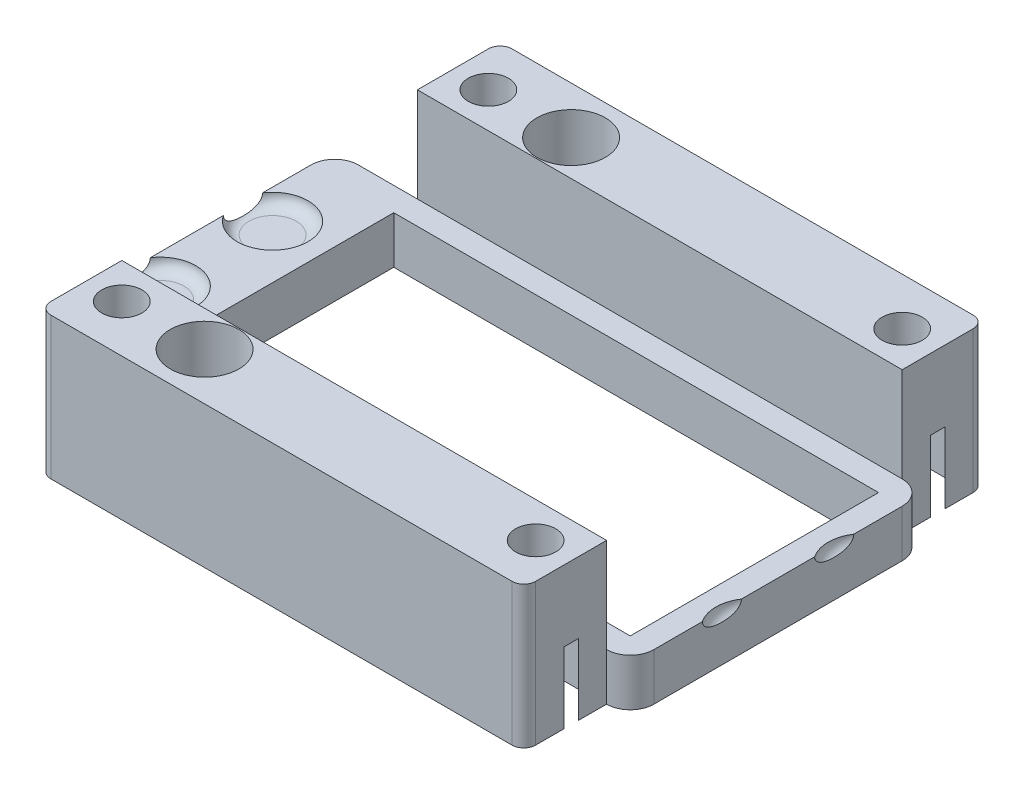
SolidWorks part; units mm, degrees
ref_plane "前视基准面" through (0, 0, 0) normal (0, 0, 1) x (1, 0, 0)
ref_plane "上视基准面" through (0, 0, 0) normal (0, 1, 0) x (1, 0, 0)
ref_plane "右视基准面" through (0, 0, 0) normal (1, 0, 0) x (0, 0, -1)
sketch "草图1" plane through (0, 0, 0) normal (0, 1, 0) x (1, 0, 0)
  line L1 (-20, 10) -> (20, 10)
  line L2 (-20, 10) -> (-20, -10)
  line L3 (-20, -10) -> (20, -10)
  line L4 (20, 10) -> (20, -10)
  line L5 (-20, 10) -> (20, -10) construction
  line L6 (-20, -10) -> (20, 10) construction
  line L7 (-20.5, 10.5) -> (20.5, 10.5)
  line L8 (-20.5, 10.5) -> (-20.5, -10.5)
  line L9 (-20.5, -10.5) -> (20.5, -10.5)
  line L10 (20.5, 10.5) -> (20.5, -10.5)
  line L11 (-20.5, 10.5) -> (20.5, -10.5) construction
  line L12 (-20.5, -10.5) -> (20.5, 10.5) construction
  line L13 (-22.5, 12.5) -> (22.5, 12.5)
  line L14 (-22.5, 12.5) -> (-22.5, -12.5)
  line L15 (-22.5, -12.5) -> (22.5, -12.5)
  line L16 (22.5, 12.5) -> (22.5, -12.5)
  line L17 (-22.5, 12.5) -> (22.5, -12.5) construction
  line L18 (-22.5, -12.5) -> (22.5, 12.5) construction
  line L19 (-22.5, 12.5) -> (-27.5, 12.5)
  line L20 (-22.5, 12.5) -> (-22.5, -12.5)
  line L21 (-22.5, -12.5) -> (-27.5, -12.5)
  line L22 (-27.5, 12.5) -> (-27.5, -12.5)
  point P0 (0, 0)
  point P5 (0, 0)
  point P11 (0, 0)
  dimension "D1" = 5
  dimension "D2" = 25
  dimension "D3" = 45
extrude "凸台-拉伸1" add sketch "草图1" along normal blind 2 and the other way blind 2 contours L19 L22 L21 L14 | L16 L13 L14 L15 L7 L10 L9 L8 region at (0, 0, -11.9852) region at (-25, 0, 0)
sketch "草图2" plane through (0, 2, 0) normal (0, 1, 0) x (1, 0, 0)
  line L0 (-20.5, 10.5) -> (-20.5, -10.5) construction
  line L1 (-20.5, 0) -> (-27.5, 0)
  line L2 (-27.5, 12.5) -> (-27.5, -12.5) construction
  line L3 (29.5, 0) -> (22.5, 0)
  circle A0 centre (-25, 4.75) radius 3
  circle A1 centre (-25, -4.75) radius 3
  circle A2 centre (25, 4.75) radius 3
  circle A3 centre (25, -4.75) radius 3
  point P0 (-25, 4.75)
  point P7 (-20.5, 0)
  point P8 (-25, 0)
  point P14 (25, 4.75)
  point P19 (29.5, 0)
  point P20 (25, 0)
  line M3 (-27.5, 12.5) -> (-27.5, -12.5)
  line M5 (22.5, -12.5) -> (22.5, 12.5)
  dimension "D2" = 9.5
  dimension "D1" = 4.5
  dimension "D3" = 4.75
extrude "切除-拉伸1" cut sketch "草图2" against normal blind 1 contours A0 M3 | A1 M3 | A2 M5 | A3 M5 | A3 M5 | A3 region at (-24.888, 2, -4.75) region at (-24.888, 2, 4.75) region at (25.112, 2, 4.75) region at (22.2985, 2, 4.75) region at (22.2985, 2, -4.75)
fillet "圆角1" radius 1 4 edges at (22, 1, -4.75) (22, 1, 4.75) (-22, 1, 4.75) (-22, 1, -4.75)
sketch "草图3" plane through (0, 0, 0) normal (0, 1, 0) x (1, 0, 0)
  line L1 (20.5, 10.5) -> (-20.5, 10.5)
  line L2 (20.5, 10.5) -> (20.5, -10.5)
  line L3 (20.5, -10.5) -> (-20.5, -10.5)
  line L4 (-20.5, 10.5) -> (-20.5, -10.5)
  line L5 (22.5, 12.5) -> (-27.5, 12.5)
  line L6 (22.5, 12.5) -> (22.5, -12.5)
  line L7 (22.5, -12.5) -> (-27.5, -12.5)
  line L8 (-27.5, 12.5) -> (-27.5, -12.5)
  line L9 (20.5, 12.5) -> (-20.5, 12.5)
  line L10 (20.5, 12.5) -> (20.5, 18.5)
  line L11 (20.5, 18.5) -> (-20.5, 18.5)
  line L12 (-20.5, 12.5) -> (-20.5, 18.5)
  line L13 (20.5, -12.5) -> (-20.5, -12.5)
  line L14 (20.5, -12.5) -> (20.5, -18.5)
  line L15 (20.5, -18.5) -> (-20.5, -18.5)
  line L16 (-20.5, -12.5) -> (-20.5, -18.5)
extrude "凸台-拉伸2" add sketch "草图3" along normal blind 10 and the other way blind 2 contours L12 L5 L10 L11 | L7 L16 L15 L14 region at (0, 0, -15.5) region at (0, 0, 15.5)
sketch "草图4" plane through (0, 10, 0) normal (0, 1, 0) x (1, 0, 0)
  line L0 (0, 0) -> (-20.5, 0)
  line L1 (-20.5, 12.5) -> (20.5, 12.5)
  line L2 (-20.5, 12.5) -> (-20.5, 18.5)
  line L3 (-20.5, 18.5) -> (20.5, 18.5)
  line L4 (20.5, 12.5) -> (20.5, 18.5)
  line L5 (-20.5, 10.5) -> (-20.5, -10.5) construction
  circle A0 centre (-10.5, 15.5) radius 2.9
  circle A1 centre (-10.5, -15.5) radius 2.9
  dimension "D1" = 10
extrude "切除-拉伸2" cut sketch "草图4" against normal blind 6 contours A0 | A1 region at (-10.5, 10, -15.5) region at (-10.5, 10, 15.5)
sketch "草图5" plane through (0, 4, 0) normal (0, 1, 0) x (1, 0, 0)
  circle A0 centre (-10.5, 15.5) radius 1.7
  circle A1 centre (-10.5, -15.5) radius 1.7
  dimension "D1" = 3.4
  dimension "D2" = 3.4
extrude "切除-拉伸3" cut sketch "草图5" against normal blind 6
sketch "草图6" plane through (0, -2, 0) normal (0, -1, 0) x (1, 0, 0)
  line L0 (14.1514, -15.5) -> (15.8257, -18.4)
  line L1 (20.5, -10.5) -> (-20.5, -10.5)
  line L2 (20.5, -10.5) -> (20.5, -18.5)
  line L3 (20.5, -18.5) -> (-20.5, -18.5)
  line L4 (-20.5, -10.5) -> (-20.5, -18.5)
  line L5 (-20.8486, -15.5) -> (-19.1743, -18.4)
  line L6 (-19.1743, -18.4) -> (-15.8257, -18.4)
  line L7 (-15.8257, -18.4) -> (-14.1514, -15.5)
  line L8 (-14.1514, -15.5) -> (-15.8257, -12.6)
  line L9 (-15.8257, -12.6) -> (-19.1743, -12.6)
  line L10 (-19.1743, -12.6) -> (-20.8486, -15.5)
  line L11 (15.8257, -18.4) -> (19.1743, -18.4)
  line L12 (19.1743, -18.4) -> (20.8486, -15.5)
  line L13 (20.8486, -15.5) -> (19.1743, -12.6)
  line L14 (19.1743, -12.6) -> (15.8257, -12.6)
  line L15 (15.8257, -12.6) -> (14.1514, -15.5)
  line L16 (14.1514, 15.5) -> (15.8257, 12.6)
  line L17 (15.8257, 12.6) -> (19.1743, 12.6)
  line L18 (19.1743, 12.6) -> (20.8486, 15.5)
  line L19 (20.8486, 15.5) -> (19.1743, 18.4)
  line L20 (19.1743, 18.4) -> (15.8257, 18.4)
  line L21 (15.8257, 18.4) -> (14.1514, 15.5)
  line L22 (-20.8486, 15.5) -> (-19.1743, 12.6)
  line L23 (-19.1743, 12.6) -> (-15.8257, 12.6)
  line L24 (-15.8257, 12.6) -> (-14.1514, 15.5)
  line L25 (-14.1514, 15.5) -> (-15.8257, 18.4)
  line L26 (-15.8257, 18.4) -> (-19.1743, 18.4)
  line L27 (-19.1743, 18.4) -> (-20.8486, 15.5)
  circle A0 centre (-17.5, -15.5) radius 2.9 construction
  circle A1 centre (17.5, -15.5) radius 2.9 construction
  circle A2 centre (17.5, 15.5) radius 2.9 construction
  circle A3 centre (-17.5, 15.5) radius 2.9 construction
  line M14 (20.5, 12.5) -> (20.5, 18.5)
  line M18 (-20.5, 18.5) -> (-20.5, 12.5)
  dimension "D1" = 5.8
  dimension "D2" = 3
  dimension "D3" = 8
  dimension "D4" = 3
  dimension "D5" = 2
extrude "切除-拉伸6" cut sketch "草图6" against normal blind 6 contours L9 L10 L5 L6 L7 L8 | L14 L15 L0 L11 L12 L2 L13 | L20 L21 L16 L17 L18 L19 M14 | L26 L27 L22 L23 L24 L25 M18 region at (17.4773, -2, -15.5) region at (-17.4773, -2, -15.5) region at (17.4773, -2, 15.5) region at (-17.4773, -2, 15.5)
sketch "草图7" plane through (0, 4, 0) normal (0, -1, 0) x (1, 0, 0)
  circle A0 centre (-17.5, -15.5) radius 1.7
  circle A1 centre (17.5, -15.5) radius 1.7
  circle A2 centre (17.5, 15.5) radius 1.7
  circle A3 centre (-17.5, 15.5) radius 1.7
  dimension "D1" = 2
extrude "切除-拉伸7" cut sketch "草图7" against normal through all
sketch "草图8" plane through (0, 0, 0) normal (0, 1, 0) x (1, 0, 0)
  line L1 (-20.5, -18.5) -> (20.5, -18.5)
  line L2 (-20.5, -18.5) -> (-20.5, -19.5)
  line L3 (-20.5, -19.5) -> (20.5, -19.5)
  line L4 (20.5, -18.5) -> (20.5, -19.5)
  line L5 (-20.5, 18.5) -> (20.5, 18.5)
  line L6 (-20.5, 18.5) -> (-20.5, 19.5)
  line L7 (-20.5, 19.5) -> (20.5, 19.5)
  line L8 (20.5, 18.5) -> (20.5, 19.5)
extrude "凸台-拉伸3" add sketch "草图8" along normal blind 10 and the other way blind 2
fillet "圆角4" radius 1 4 edges at (-20.5, 4, 19.5) (20.5, 4, 19.5) (20.5, 4, -19.5) (-20.5, 4, -19.5)
fillet "圆角5" radius 2 4 edges at (22.5, 0, -12.5) (22.5, 0, 12.5) (-27.5, 0, -12.5) (-27.5, 0, 12.5)
